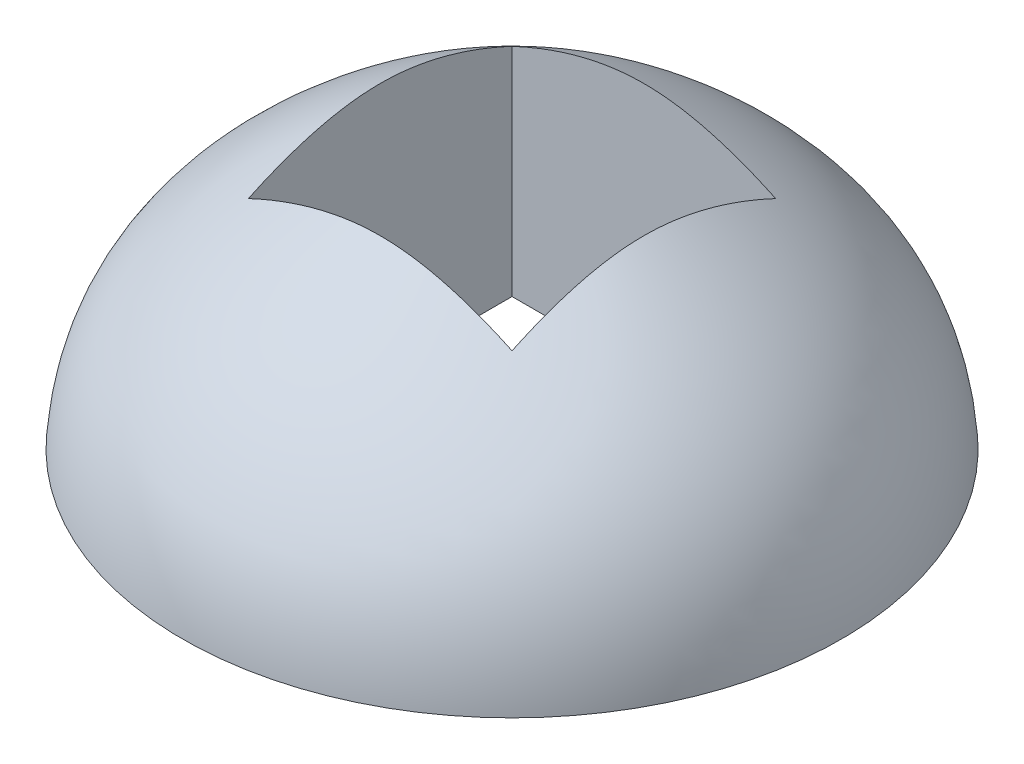
SolidWorks part; units mm, degrees
ref_plane "Front Plane" through (0, 0, 0) normal (0, 0, 1) x (1, 0, 0)
ref_plane "Top Plane" through (0, 0, 0) normal (0, 1, 0) x (1, 0, 0)
ref_plane "Right Plane" through (0, 0, 0) normal (1, 0, 0) x (0, 0, -1)
sketch "Sketch1" plane through (0, 0, 0) normal (0, 0, 1) x (1, 0, 0)
  line L0 (0, 0) -> (0, 0.5)
  line L1 (0, 0) -> (0.5, 0)
  spline S0 degree 3 poles (0.5, 0) (0.4803, 0.2853) (0.196, 0.3626) (0, 0.5) knots 0 0 0 0 1 1 1 1
  dimension "D1" = 0.5
  dimension "D2" = 0.5
revolve "Revolve1" add sketch "Sketch1" angle 360 about L0
sketch "Sketch2" plane through (0, 0, 0) normal (0, -1, 0) x (1, 0, 0)
  line L1 (-0.2, -0.2) -> (0.2, -0.2)
  line L2 (-0.2, -0.2) -> (-0.2, 0.2)
  line L3 (-0.2, 0.2) -> (0.2, 0.2)
  line L4 (0.2, -0.2) -> (0.2, 0.2)
  line L5 (-0.2, -0.2) -> (0.2, 0.2) construction
  line L6 (-0.2, 0.2) -> (0.2, -0.2) construction
  point P0 (0, 0)
  dimension "D1" = 0.4
extrude "Cut-Extrude1" cut sketch "Sketch2" against normal through all
